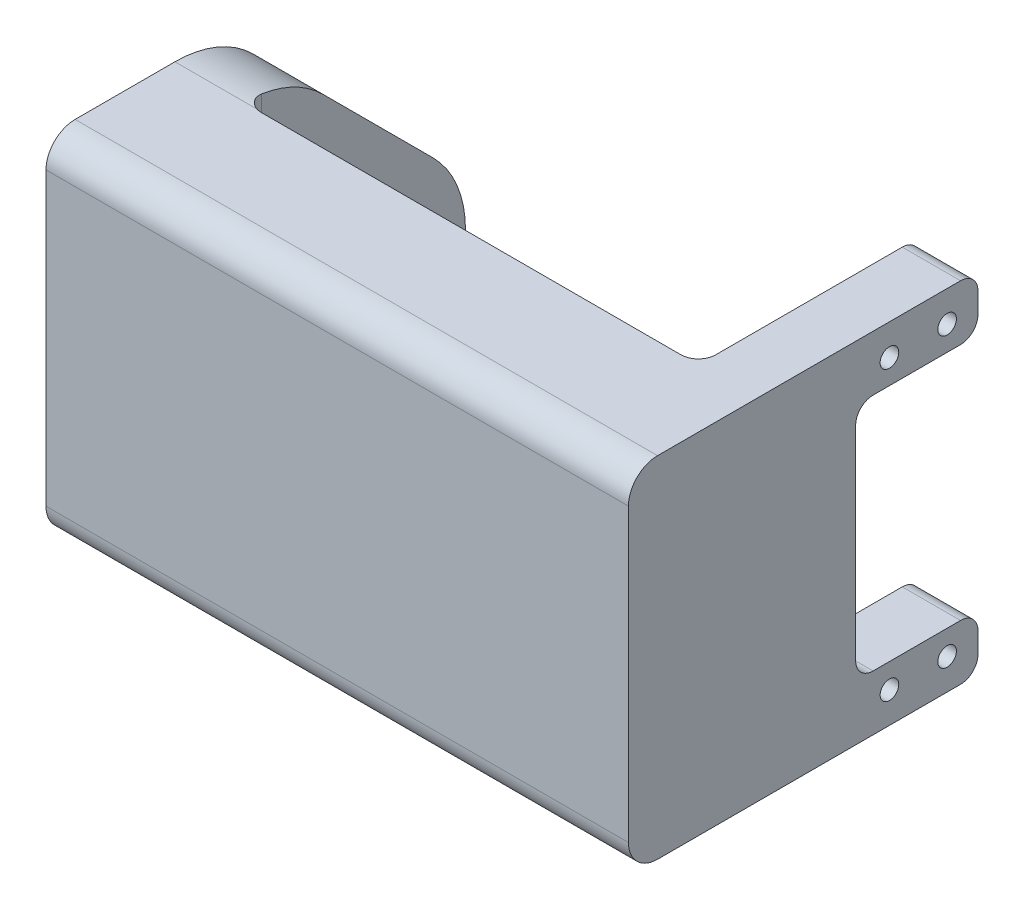
SolidWorks part; units mm, degrees
ref_plane "Front Plane" through (0, 0, 0) normal (0, 0, 1) x (1, 0, 0)
ref_plane "Top Plane" through (0, 0, 0) normal (0, 1, 0) x (1, 0, 0)
ref_plane "Right Plane" through (0, 0, 0) normal (1, 0, 0) x (0, 0, -1)
sketch "Sketch1" plane through (0, 0, 0) normal (0, 1, 0) x (1, 0, 0)
  line L0 (0, 0) -> (0, 60)
  line L1 (0, 60) -> (12, 60)
  line L2 (12, 60) -> (12, 22)
  line L3 (12, 22) -> (89.97, 22)
  line L4 (89.97, 22) -> (89.97, 60)
  line L5 (89.97, 60) -> (99.97, 60)
  line L6 (99.97, 60) -> (99.97, 0)
  line L7 (99.97, 0) -> (0, 0)
  dimension "D1" = 12
  dimension "D2" = 38
  dimension "D3" = 10
  dimension "D4" = 77.97
  dimension "D5" = 60
extrude "Boss-Extrude1" add sketch "Sketch1" along normal blind 60
sketch "Sketch2" plane through (99.97, 0, 0) normal (1, 0, 0) x (0, 0, -1)
  line L0 (44.8, 5.305) -> (44.8, 54.695) construction
  line L1 (0, 30) -> (44.8, 30) construction
  line L2 (0, 60) -> (0, 0) construction
  line L3 (9.9, 30) -> (54.7, 30) construction
  line L4 (60, 60) -> (60, 0) construction
  line L5 (49.75, 54.695) -> (49.75, 19.58) construction
  line L6 (44.8, 54.695) -> (54.7, 54.695) construction
  circle A0 centre (44.8, 54.695) radius 1.6
  circle A1 centre (44.8, 5.305) radius 1.6
  circle A2 centre (54.7, 54.695) radius 1.6
  circle A3 centre (54.7, 5.305) radius 1.6
  circle A4 centre (49.75, 19.58) radius 8
  circle A5 centre (49.75, 19.58) radius 6
  dimension "D2" = 3.2
  dimension "D5" = 5.3
  dimension "D7" = 16
  dimension "D1" = 49.39
  dimension "D4" = 9.9
  dimension "D6" = 14.275
  dimension "D8" = 2
  dimension "D3" = 2
extrude "Cut-Extrude1" cut sketch "Sketch2" against normal up to next contours A0 | A2 | A3 | A1 region at (99.97, 54.695, -44.8) region at (99.97, 5.305, -44.8) region at (99.97, 54.695, -54.7) region at (99.97, 5.305, -54.7)
sketch "Sketch3" plane through (99.97, 0, 0) normal (1, 0, 0) x (0, 0, -1)
  line L0 (60, 60) -> (60, 0) construction
  line L1 (60, 50.5) -> (39, 50.5)
  line L2 (60, 50.5) -> (60, 9.5)
  line L3 (60, 9.5) -> (39, 9.5)
  line L4 (39, 50.5) -> (39, 9.5)
  point P8 (60, 30)
  dimension "D1" = 41
  dimension "D2" = 21
extrude "Cut-Extrude2" cut sketch "Sketch3" against normal up to next
extrude "Cut-Extrude3" cut sketch "Sketch2<3>" against normal blind 5 from surface contours A4 A5 | A5 region at (99.97, 19.58, -41.9763) region at (99.97, 19.58, -49.75) starting at face at (12, 30, -41)
sketch "Sketch2<3>" plane through (99.97, 0, 0) normal (1, 0, 0) x (0, 0, -1) same geometry as "Sketch2"
extrude "Cut-Extrude4" cut sketch "Sketch2<4>" against normal through all from surface contours A5 region at (99.97, 19.58, -49.75) starting at face at (7, 19.58, -41.75)
sketch "Sketch2<4>" plane through (99.97, 0, 0) normal (1, 0, 0) x (0, 0, -1) same geometry as "Sketch2"
chamfer "Chamfer1" distance 30 angle 45 1 edges at (6, 60, -60)
fillet "Fillet1" radius 19 3 edges at (6, 0, -60) (6, 60, -30) (6, 30, -60)
fillet "Fillet2" radius 3 8 edges at (12, 30, -22) (89.97, 30, -22) (94.97, 50.5, -39) (94.97, 9.5, -39) (94.97, 0, -60) (94.97, 9.5, -60) (94.97, 50.5, -60) (94.97, 60, -60)
fillet "Fillet3" radius 5 2 edges at (49.985, 0, 0) (49.985, 60, 0)
